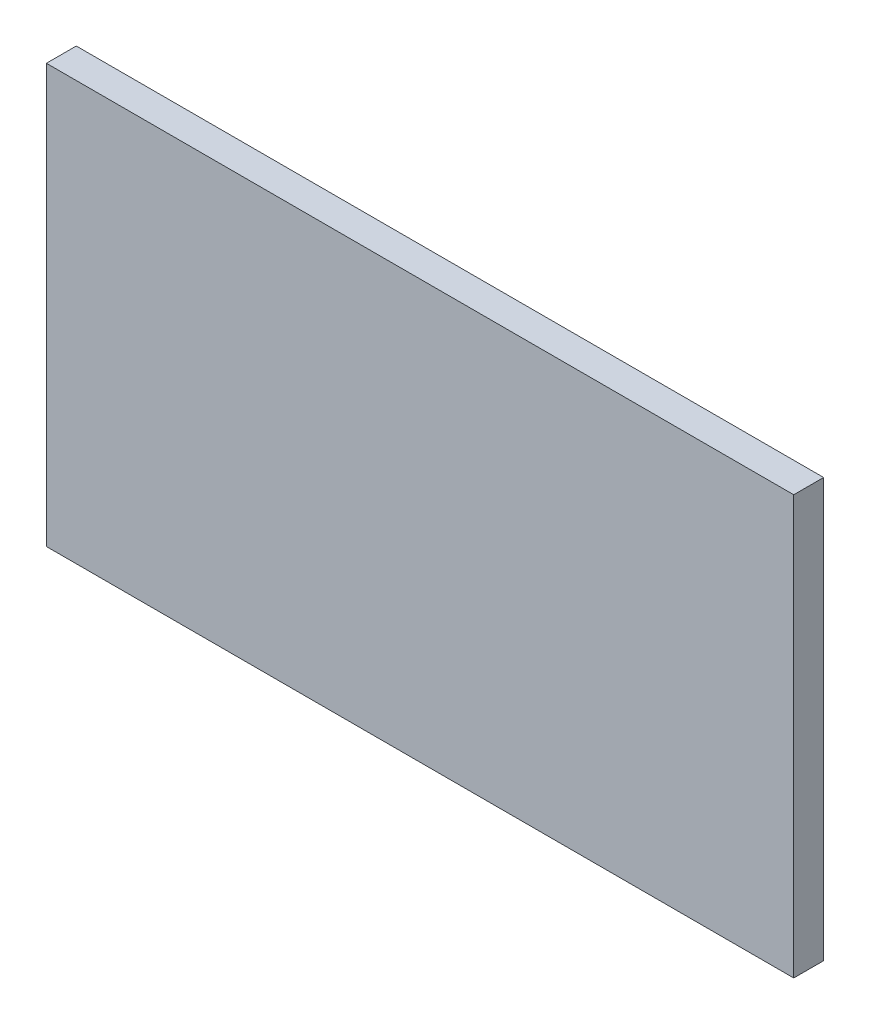
SolidWorks part; units mm, degrees
ref_plane "Front Plane" through (0, 0, 0) normal (0, 0, 1) x (1, 0, 0)
ref_plane "Top Plane" through (0, 0, 0) normal (0, 1, 0) x (1, 0, 0)
ref_plane "Right Plane" through (0, 0, 0) normal (1, 0, 0) x (0, 0, -1)
sketch "Sketch1" plane through (0, 0, 0) normal (0, 0, 1) x (1, 0, 0)
  line L1 (158.75, -88.9) -> (-158.75, -88.9)
  line L2 (158.75, -88.9) -> (158.75, 88.9)
  line L3 (158.75, 88.9) -> (-158.75, 88.9)
  line L4 (-158.75, -88.9) -> (-158.75, 88.9)
  line L5 (158.75, -88.9) -> (-158.75, 88.9) construction
  line L6 (158.75, 88.9) -> (-158.75, -88.9) construction
  point P0 (0, 0)
  dimension "D1" = 177.8
  dimension "D2" = 317.5
extrude "Boss-Extrude1" add sketch "Sketch1" along normal blind 12.7
ref_point "Point2"
